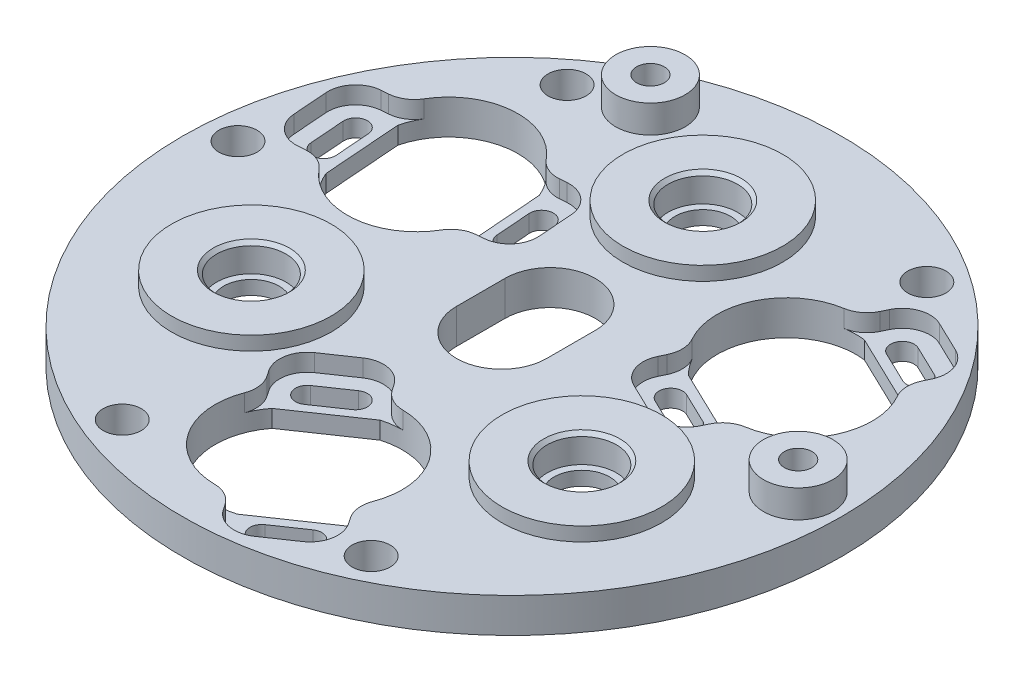
SolidWorks part; units mm, degrees
note: The reader was unsure of these and kept them because the rebuilt part matched: shared geometry of "Esquisse8<2>".
ref_plane "Plan de face" through (0, 0, 0) normal (0, 0, 1) x (1, 0, 0)
ref_plane "Plan de dessus" through (0, 0, 0) normal (0, 1, 0) x (1, 0, 0)
ref_plane "Plan de droite" through (0, 0, 0) normal (1, 0, 0) x (0, 0, -1)
sketch "Sketch2" plane through (0, 0, 0) normal (1, 0, 0) x (0, 0, -1)
  line L0 (27.5, 24.4363) -> (27.5, -19.6412) construction
  line L1 (0, -21.9713) -> (0, 23.6588) construction
  line L2 (-10.4637, 0) -> (17.1572, 0) construction
  line L3 (21, 0) -> (21, -3)
  line L5 (22.5, -1) -> (22.5, 3)
  line L7 (22.5, -1) -> (23.5, -1)
  line L8 (23.5, -1) -> (23.5, -3)
  line L9 (23.5, -3) -> (21, -3)
  line L11 (16, 3) -> (16, -4)
  line L12 (16, -4) -> (17.5, -4)
  line L13 (17.5, -4) -> (17.5, 0)
  line L14 (17.5, 0) -> (21, 0)
  line L20 (22.5, 3) -> (16, 3)
  dimension "D1" = 27.5
  dimension "D2" = 4
  dimension "D3" = 2
  dimension "D4" = 3
  dimension "D5" = 5
  dimension "D6" = 4
  dimension "D7" = 1.5
  dimension "D8" = 10
  dimension "D9" = 1.5
  dimension "D10" = 4
revolve "Revolve1" add sketch "Sketch2" angle 360 about L0
pattern_circular "CirPattern1" count 3 over 360 about axis through (0, 0, 0) along (0, 1, 0) of bodies 104
sketch "Sketch3" plane through (0, 0, 0) normal (0, 1, 0) x (1, 0, 0)
  line L0 (0, 0) -> (41.25, 0) construction
  line L1 (0, 0) -> (0, 47.5) construction
  line L2 (0, 0) -> (-17.433, 37.3852) construction
  line L3 (0, 0) -> (0, -30) construction
  line L4 (0, 0) -> (-25.9808, 15) construction
  line L5 (0, 0) -> (25.9808, 15) construction
  line L6 (0, -1.5) -> (0, 5.5) construction
  line L7 (-6.5, -1.5) -> (-6.5, 5.5)
  line L8 (6.5, -1.5) -> (6.5, 5.5)
  circle A0 centre (0, 0) radius 47.5
  circle A1 centre (0, 27.5) radius 6.5
  circle A2 centre (23.8157, -13.75) radius 6.5
  circle A3 centre (-23.8157, -13.75) radius 6.5
  circle A4 centre (0, 0) radius 27.5 construction
  arc A5 (-6.5, -1.5) -> (6.5, -1.5) centre (0, -1.5) ccw
  arc A6 (6.5, 5.5) -> (-6.5, 5.5) centre (0, 5.5) ccw
  circle A12 centre (0, 0) radius 7.5 construction
  circle A13 centre (-23.8157, -13.75) radius 11.5
  circle A14 centre (23.8157, -13.75) radius 11.5
  circle A15 centre (0, 27.5) radius 11.5
  circle A26 centre (0, 0) radius 30 construction
  circle A27 centre (0, 0) radius 41.25 construction
  circle A28 centre (0, -30) radius 1.7 construction
  circle A29 centre (-25.9808, 15) radius 1.7 construction
  circle A30 centre (25.9808, 15) radius 1.7 construction
  circle A31 centre (-17.433, 37.3852) radius 1.2 construction
  circle A32 centre (41.25, 0) radius 1.2 construction
  circle A33 centre (0, -30) radius 6 construction
  circle A34 centre (0, -30) radius 10
  circle A35 centre (25.9808, 15) radius 6 construction
  circle A36 centre (25.9808, 15) radius 10
  circle A37 centre (-25.9808, 15) radius 6 construction
  circle A38 centre (-25.9808, 15) radius 10
  circle A39 centre (-17.433, 37.3852) radius 2 construction
  circle A40 centre (-17.433, 37.3852) radius 4 construction
  circle A41 centre (41.25, 0) radius 2 construction
  circle A42 centre (41.25, 0) radius 4 construction
  circle A43 centre (-23.8157, -13.75) radius 6.5 construction
  point P17 (0, 2)
  point P35 (0, 0)
  dimension "D1" = 95
  dimension "D7" = 25
  dimension "D10" = 15
  dimension "D2" = 23
  dimension "D5" = 3.4
  dimension "D6" = 3
  dimension "D11" = 2
  dimension "D12" = 12
  dimension "D3" = 82.5
  dimension "D4" = 60
  dimension "D8" = 2.4
  dimension "D9" = 4
  dimension "D13" = 20
  dimension "D16" = 6.5
  dimension "D14" = 1.5
  dimension "D15" = 5.5
extrude "Boss-Extrude3" add sketch "Sketch3" along normal blind 5 from surface at -4
sketch "Esquisse4" plane through (0, 0, 0) normal (1, 0, 0) x (0, 0, -1)
  line L0 (-30, 11.1476) -> (-30, -4.6583) construction
  line L1 (0, 0) -> (0, 30.7253) construction
  line L2 (-38, -4.6) -> (-38, -0.6)
  line L3 (-38, -0.6) -> (-38.4, -0.6)
  line L4 (-38.4, -0.6) -> (-38.4, 0.5)
  line L5 (-38.4, 0.5) -> (-38, 0.5)
  line L6 (-38, 0.5) -> (-38, 1.5)
  line L8 (-40, 1.5) -> (-40, -6.1)
  line L10 (-40, 1.5) -> (-38, 1.5)
  line L11 (-40, -6.1) -> (-36.5, -6.1)
  line L14 (-36.5, -6.1) -> (-36.5, -4.6)
  line L15 (-36.5, -4.6) -> (-38, -4.6)
  line L16 (47.5, 1) -> (-47.5, 1) construction
  dimension "D1" = 4
  dimension "D2" = 8.4
  dimension "D3" = 8
  dimension "D4" = 2
  dimension "D5" = 0.5
  dimension "D6" = 1
  dimension "D7" = 1.1
  dimension "D8" = 1.5
  dimension "D9" = 1.5
revolve "Révolution1" add sketch "Esquisse4" angle 360 about L0
pattern_circular "Répétition circulaire1" count 3 over 360 about axis through (0, 0, 0) along (0, 1, 0) of "Révolution1"
sketch "Esquisse6" plane through (0, 1, 0) normal (0, 1, 0) x (1, 0, 0)
  line L0 (0, 27.5) -> (25.9808, 15) construction
  line L3 (23.2774, 16.3007) -> (27.783, 14.1329) construction
  line L4 (27.6129, 25.3119) -> (32.1186, 23.1442)
  line L5 (18.9418, 7.2894) -> (23.4475, 5.1216)
  line L6 (2.4781, -28.3091) -> (-1.6521, -31.1272) construction
  line L7 (8.1143, -36.5695) -> (3.9841, -39.3876)
  line L8 (-3.1581, -20.0488) -> (-7.2883, -22.8669)
  line L9 (-25.7555, 12.0085) -> (-26.1309, 16.9944) construction
  line L10 (-35.7272, 11.2575) -> (-36.1027, 16.2434)
  line L11 (-15.7837, 12.7594) -> (-16.1592, 17.7453)
  arc A3 (27.6129, 25.3119) -> (18.9418, 7.2894) centre (23.2774, 16.3007) ccw
  arc A4 (23.4475, 5.1216) -> (32.1186, 23.1442) centre (27.783, 14.1329) ccw
  arc A5 (8.1143, -36.5695) -> (-3.1581, -20.0488) centre (2.4781, -28.3091) ccw
  arc A6 (-7.2883, -22.8669) -> (3.9841, -39.3876) centre (-1.6521, -31.1272) ccw
  arc A7 (-35.7272, 11.2575) -> (-15.7837, 12.7594) centre (-25.7555, 12.0085) ccw
  arc A8 (-16.1592, 17.7453) -> (-36.1027, 16.2434) centre (-26.1309, 16.9944) ccw
  point P4 (25.5302, 15.2168)
  point P15 (0.413, -29.7182)
  point P22 (-25.9432, 14.5014)
  point P27 (0, 0)
  dimension "D3" = 10
  dimension "D1" = 3
  dimension "D2" = 2
  dimension "D4" = 3
extrude "Enlèv. mat.-Extru.2" cut sketch "Esquisse6" against normal through all both and the other way through all
chamfer "Chanfrein1" distance 0.5 angle 45 3 edges at (19.4856, 3, 11.25) (0, 3, -22.5) (-19.4856, 3, 11.25)
fillet "Congé1" radius 1 6 edges at (18.1865, 0, 10.5) (15.1554, 0, 8.75) (0, 0, -21) (0, 0, -17.5) (-18.1865, 0, 10.5) (-15.1554, 0, 8.75)
chamfer "Chanfrein3" distance 1.5 angle 45 3 edges at (0, -4, -17.5) (15.1554, -4, 8.75) (-15.1554, -4, 8.75)
sketch "Esquisse7" plane through (0, 1, 0) normal (0, 1, 0) x (1, 0, 0)
  line L0 (5.3932, -41.4527) -> (9.5234, -38.6346) construction
  line L1 (3.1387, -38.1485) -> (7.2689, -35.3304)
  line L2 (7.6477, -44.7568) -> (11.7779, -41.9387)
  line L3 (-8.6973, -20.8018) -> (-4.5672, -17.9837) construction
  line L4 (-10.9518, -17.4977) -> (-6.8217, -14.6796)
  line L5 (-6.4428, -24.106) -> (-2.3127, -21.2879)
  line L6 (-38.896, 20.0444) -> (-35.5706, 20.2948)
  line L7 (-7.2883, -22.8669) -> (-3.1581, -20.0488) construction
  line L8 (8.1143, -36.5695) -> (3.9841, -39.3876) construction
  line L9 (7.4583, -40.0436) -> (-6.6323, -19.3928) construction
  line L10 (-9.9124, -36.7635) -> (10.7384, -22.6729) construction
  line L11 (2.0891, -43.7071) -> (0.2095, -40.9524)
  line L12 (12.8275, -36.3801) -> (10.9479, -33.6254)
  line L13 (-12.0015, -23.0563) -> (-10.1219, -25.811)
  line L14 (-1.263, -15.7292) -> (0.6166, -18.4839)
  line L15 (8.1143, -36.5695) -> (3.9841, -39.3876)
  line L16 (-7.2883, -22.8669) -> (-3.1581, -20.0488)
  line L17 (-37.9198, 7.0811) -> (-34.5944, 7.3315)
  line L18 (-35.7272, 11.2575) -> (-36.1027, 16.2434)
  line L19 (-16.1592, 17.7453) -> (-15.7837, 12.7594)
  line L20 (-12.9904, 8.9584) -> (-16.3158, 8.708)
  line L21 (-13.9666, 21.9217) -> (-17.2921, 21.6713)
  line L22 (-26.8819, 26.9661) -> (-25.0045, 2.0367) construction
  line L23 (-38.4079, 13.5627) -> (-13.4785, 15.4401) construction
  line L24 (-38.5957, 16.0557) -> (-38.2202, 11.0698) construction
  line L25 (-34.6069, 16.3561) -> (-34.2315, 11.3702)
  line L26 (-42.5844, 15.7553) -> (-42.2089, 10.7694)
  line L27 (-13.6662, 17.933) -> (-13.2908, 12.9471) construction
  line L28 (-9.6775, 18.2334) -> (-9.3021, 13.2475)
  line L29 (-17.655, 17.6327) -> (-17.2795, 12.6468)
  line L30 (36.807, 23.6628) -> (35.3611, 20.6576)
  line L31 (25.0923, 29.299) -> (23.6465, 26.2939)
  line L32 (27.6129, 25.3119) -> (32.1186, 23.1442)
  line L33 (23.4475, 5.1216) -> (18.9418, 7.2894)
  line L34 (14.2534, 6.7708) -> (15.6993, 9.7759)
  line L35 (25.9681, 1.1346) -> (27.4139, 4.1397)
  line L36 (36.7943, 9.7973) -> (14.2661, 20.6362) construction
  line L37 (30.9496, 26.4809) -> (20.1108, 3.9527) construction
  line L38 (33.2025, 25.397) -> (28.6968, 27.5648) construction
  line L39 (31.4682, 21.7925) -> (26.9626, 23.9602)
  line L40 (34.9367, 29.0015) -> (30.431, 31.1693)
  line L41 (22.3636, 2.8688) -> (17.8579, 5.0366) construction
  line L42 (20.6294, -0.7357) -> (16.1237, 1.4321)
  line L43 (24.0978, 6.4733) -> (19.5922, 8.6411)
  arc A0 (3.1387, -38.1485) -> (7.6477, -44.7568) centre (5.3932, -41.4527) ccw
  arc A1 (11.7779, -41.9387) -> (7.2689, -35.3304) centre (9.5234, -38.6346) ccw
  arc A2 (-10.9518, -17.4977) -> (-6.4428, -24.106) centre (-8.6973, -20.8018) ccw
  arc A3 (-2.3127, -21.2879) -> (-6.8217, -14.6796) centre (-4.5672, -17.9837) ccw
  arc A4 (-7.2883, -22.8669) -> (3.9841, -39.3876) centre (-1.6521, -31.1272) ccw construction
  arc A5 (8.1143, -36.5695) -> (-3.1581, -20.0488) centre (2.4781, -28.3091) ccw construction
  arc A6 (8.1143, -36.5695) -> (10.9479, -33.6254) centre (2.4781, -28.3091) ccw
  arc A7 (-7.2883, -22.8669) -> (-10.1219, -25.811) centre (-1.6521, -31.1272) ccw
  arc A8 (0.2095, -40.9524) -> (3.9841, -39.3876) centre (-1.6521, -31.1272) ccw
  arc A9 (0.6166, -18.4839) -> (-3.1581, -20.0488) centre (2.4781, -28.3091) ccw
  arc A10 (-35.7272, 11.2575) -> (-34.5944, 7.3315) centre (-25.7555, 12.0085) ccw
  arc A11 (-35.5706, 20.2948) -> (-36.1027, 16.2434) centre (-26.1309, 16.9944) ccw
  arc A12 (-16.1592, 17.7453) -> (-17.2921, 21.6713) centre (-26.1309, 16.9944) ccw
  arc A13 (-16.3158, 8.708) -> (-15.7837, 12.7594) centre (-25.7555, 12.0085) ccw
  arc A14 (-34.6069, 16.3561) -> (-42.5844, 15.7553) centre (-38.5957, 16.0557) ccw
  arc A15 (-42.2089, 10.7694) -> (-34.2315, 11.3702) centre (-38.2202, 11.0698) ccw
  arc A16 (-9.6775, 18.2334) -> (-17.655, 17.6327) centre (-13.6662, 17.933) ccw
  arc A17 (-17.2795, 12.6468) -> (-9.3021, 13.2475) centre (-13.2908, 12.9471) ccw
  arc A18 (27.6129, 25.3119) -> (23.6465, 26.2939) centre (23.2774, 16.3007) ccw
  arc A19 (35.3611, 20.6576) -> (32.1186, 23.1442) centre (27.783, 14.1329) ccw
  arc A20 (23.4475, 5.1216) -> (27.4139, 4.1397) centre (27.783, 14.1329) ccw
  arc A21 (15.6993, 9.7759) -> (18.9418, 7.2894) centre (23.2774, 16.3007) ccw
  arc A22 (31.4682, 21.7925) -> (34.9367, 29.0015) centre (33.2025, 25.397) ccw
  arc A23 (30.431, 31.1693) -> (26.9626, 23.9602) centre (28.6968, 27.5648) ccw
  arc A24 (20.6294, -0.7357) -> (24.0978, 6.4733) centre (22.3636, 2.8688) ccw
  arc A25 (19.5922, 8.6411) -> (16.1237, 1.4321) centre (17.8579, 5.0366) ccw
  point P2 (7.4583, -40.0436)
  point P7 (-6.6323, -19.3928)
  point P20 (6.0492, -37.9785)
  point P21 (-5.2232, -21.4579)
  point P30 (0.413, -29.7182)
  point P40 (-38.4079, 13.5627)
  point P45 (-13.4785, 15.4401)
  point P72 (30.9496, 26.4809)
  point P77 (20.1108, 3.9527)
  point P102 (0, 0)
  circle M14 centre (-23.8157, -13.75) radius 11.5
  circle M15 centre (23.8157, -13.75) radius 11.5
  circle M16 centre (0, 27.5) radius 11.5
  line M17 (-7.2883, -22.8669) -> (-3.1581, -20.0488)
  arc M18 (-3.1581, -20.0488) -> (8.1143, -36.5695) centre (2.4781, -28.3091) cw
  line M19 (8.1143, -36.5695) -> (3.9841, -39.3876)
  arc M20 (3.9841, -39.3876) -> (-7.2883, -22.8669) centre (-1.6521, -31.1272) cw
  line M21 (23.4475, 5.1216) -> (18.9418, 7.2894)
  arc M22 (18.9418, 7.2894) -> (27.6129, 25.3119) centre (23.2774, 16.3007) cw
  line M23 (27.6129, 25.3119) -> (32.1186, 23.1442)
  arc M24 (32.1186, 23.1442) -> (23.4475, 5.1216) centre (27.783, 14.1329) cw
  line M25 (-16.1592, 17.7453) -> (-15.7837, 12.7594)
  arc M26 (-15.7837, 12.7594) -> (-35.7272, 11.2575) centre (-25.7555, 12.0085) cw
  line M27 (-35.7272, 11.2575) -> (-36.1027, 16.2434)
  arc M28 (-36.1027, 16.2434) -> (-16.1592, 17.7453) centre (-26.1309, 16.9944) cw
  line M29 (-6.5, -1.5) -> (-6.5, 5.5)
  arc M30 (-6.5, 5.5) -> (6.5, 5.5) centre (0, 5.5) cw
  line M31 (6.5, 5.5) -> (6.5, -1.5)
  arc M32 (6.5, -1.5) -> (-6.5, -1.5) centre (0, -1.5) cw
  dimension "D2" = 4
  dimension "D1" = 12.5
  dimension "D3" = 3
extrude "Enlèv. mat.-Extru.3" cut sketch "Esquisse7" against normal blind 2.5 contours A3 L4 A2 M18 M32 M14 M20 M17 | A3 L14 M18 | A2 L13 M20 | L2 A1 A0 M18 M19 M20 | A0 L11 M20 | A1 L12 M18 | A25 L42 A24 A20 M31 M15 M21 M22 | A25 A21 L34 | A24 L35 M24 | L40 A23 A18 A22 M23 M24 | A22 A19 L30 | A23 L31 M22 | A17 L28 A16 A12 M26 M29 M30 M16 M25 | A16 L21 M28 | A17 A13 L20 | A15 A10 A14 L26 M27 M28 | A15 L17 M26 | A14 A11 L6
sketch "Esquisse8" plane through (0, 1, 0) normal (0, 1, 0) x (1, 0, 0)
  line L0 (-8.6973, -20.8018) -> (-4.5672, -17.9837) construction
  line L1 (-9.6555, -19.3976) -> (-5.5253, -16.5795)
  line L2 (-7.7392, -22.2061) -> (-3.609, -19.388)
  line L3 (5.3932, -41.4527) -> (9.5234, -38.6346) construction
  line L4 (4.435, -40.0484) -> (8.5652, -37.2303)
  line L5 (6.3514, -42.8569) -> (10.4815, -40.0388)
  line L6 (22.3636, 2.8688) -> (17.8579, 5.0366) construction
  line L7 (21.6265, 1.3369) -> (17.1209, 3.5047)
  line L8 (23.1006, 4.4007) -> (18.595, 6.5685)
  line L9 (33.2025, 25.397) -> (28.6968, 27.5648) construction
  line L10 (32.4654, 23.8651) -> (27.9598, 26.0328)
  line L11 (33.9395, 26.9289) -> (29.4339, 29.0967)
  line L12 (-13.2908, 12.9471) -> (-13.6662, 17.933) construction
  line L13 (-14.986, 12.8195) -> (-15.3614, 17.8054)
  line L14 (-11.5956, 13.0748) -> (-11.971, 18.0607)
  line L15 (-38.2202, 11.0698) -> (-38.5957, 16.0557) construction
  line L16 (-39.9154, 10.9421) -> (-40.2909, 15.928)
  line L17 (-36.525, 11.1975) -> (-36.9005, 16.1833)
  line L18 (-9.5858, -25.0398) -> (-0.297, -18.7019)
  line L19 (1.123, -40.7345) -> (10.4118, -34.3965)
  line L20 (8.1143, -36.5695) -> (3.9841, -39.3876) construction
  line L21 (-7.2883, -22.8669) -> (-3.1581, -20.0488) construction
  line L22 (-7.2883, -22.8669) -> (-3.1581, -20.0488)
  line L23 (8.1143, -36.5695) -> (3.9841, -39.3876)
  line L24 (-16.8923, 20.8214) -> (-16.0478, 9.6082)
  line L25 (-16.1592, 17.7453) -> (-15.7837, 12.7594)
  line L26 (-35.7272, 11.2575) -> (-36.1027, 16.2434)
  line L27 (-35.8386, 19.3946) -> (-34.9942, 8.1814)
  line L28 (26.478, 4.2184) -> (16.3448, 9.0937)
  line L29 (23.4475, 5.1216) -> (18.9418, 7.2894)
  line L30 (27.6129, 25.3119) -> (32.1186, 23.1442)
  line L31 (34.7156, 21.3398) -> (24.5824, 26.2151)
  arc A0 (-9.6555, -19.3976) -> (-7.7392, -22.2061) centre (-8.6973, -20.8018) ccw
  arc A1 (-3.609, -19.388) -> (-5.5253, -16.5795) centre (-4.5672, -17.9837) ccw
  arc A2 (4.435, -40.0484) -> (6.3514, -42.8569) centre (5.3932, -41.4527) ccw
  arc A3 (10.4815, -40.0388) -> (8.5652, -37.2303) centre (9.5234, -38.6346) ccw
  arc A4 (21.6265, 1.3369) -> (23.1006, 4.4007) centre (22.3636, 2.8688) ccw
  arc A5 (18.595, 6.5685) -> (17.1209, 3.5047) centre (17.8579, 5.0366) ccw
  arc A6 (32.4654, 23.8651) -> (33.9395, 26.9289) centre (33.2025, 25.397) ccw
  arc A7 (29.4339, 29.0967) -> (27.9598, 26.0328) centre (28.6968, 27.5648) ccw
  arc A8 (-14.986, 12.8195) -> (-11.5956, 13.0748) centre (-13.2908, 12.9471) ccw
  arc A9 (-11.971, 18.0607) -> (-15.3614, 17.8054) centre (-13.6662, 17.933) ccw
  arc A10 (-39.9154, 10.9421) -> (-36.525, 11.1975) centre (-38.2202, 11.0698) ccw
  arc A11 (-36.9005, 16.1833) -> (-40.2909, 15.928) centre (-38.5957, 16.0557) ccw
  arc A12 (-7.2883, -22.8669) -> (-10.1219, -25.811) centre (-1.6521, -31.1272) ccw construction
  arc A13 (10.9479, -33.6254) -> (0.6166, -18.4839) centre (2.4781, -28.3091) ccw construction
  arc A14 (-10.1219, -25.811) -> (0.2095, -40.9524) centre (-1.6521, -31.1272) ccw construction
  arc A15 (0.6166, -18.4839) -> (-3.1581, -20.0488) centre (2.4781, -28.3091) ccw construction
  arc A16 (0.2095, -40.9524) -> (3.9841, -39.3876) centre (-1.6521, -31.1272) ccw construction
  arc A17 (8.1143, -36.5695) -> (10.9479, -33.6254) centre (2.4781, -28.3091) ccw construction
  arc A18 (-0.297, -18.7019) -> (-3.1581, -20.0488) centre (2.4781, -28.3091) ccw
  arc A19 (-7.2883, -22.8669) -> (-9.5858, -25.0398) centre (-1.6521, -31.1272) ccw
  arc A20 (1.123, -40.7345) -> (3.9841, -39.3876) centre (-1.6521, -31.1272) ccw
  arc A21 (8.1143, -36.5695) -> (10.4118, -34.3965) centre (2.4781, -28.3091) ccw
  arc A22 (-16.1592, 17.7453) -> (-16.8923, 20.8214) centre (-26.1309, 16.9944) ccw
  arc A23 (-16.0478, 9.6082) -> (-15.7837, 12.7594) centre (-25.7555, 12.0085) ccw
  arc A24 (-35.8386, 19.3946) -> (-36.1027, 16.2434) centre (-26.1309, 16.9944) ccw
  arc A25 (-35.7272, 11.2575) -> (-34.9942, 8.1814) centre (-25.7555, 12.0085) ccw
  arc A26 (23.4475, 5.1216) -> (26.478, 4.2184) centre (27.783, 14.1329) ccw
  arc A27 (16.3448, 9.0937) -> (18.9418, 7.2894) centre (23.2774, 16.3007) ccw
  arc A28 (34.7156, 21.3398) -> (32.1186, 23.1442) centre (27.783, 14.1329) ccw
  arc A29 (27.6129, 25.3119) -> (24.5824, 26.2151) centre (23.2774, 16.3007) ccw
  point P4 (-6.6323, -19.3928)
  point P9 (7.4583, -40.0436)
  point P18 (20.1108, 3.9527)
  point P27 (30.9496, 26.4809)
  point P36 (-13.4785, 15.4401)
  point P45 (-38.4079, 13.5627)
  point P98 (0, 0)
  dimension "D1" = 1.7
  dimension "D2" = 0.5
  dimension "D3" = 0.5
  dimension "D4" = 3
extrude "Enlèv. mat.-Extru.4" cut sketch "Esquisse8" against normal up to next
extrude "Boss.-Extru.1" add sketch "Esquisse8<2>" against normal up to surface (2.5 mm away) from surface at -2.5 contours L23 A21 L19 A20 | L22 A19 L18 A18 | L26 A25 L27 A24 | L30 A29 L31 A28 | L24 A23 L25 A22 | L28 A27 L29 A26 starting at face at (30.9496, -1.5, -26.4809)
sketch "Esquisse8<2>" plane through (0, 1, 0) normal (0, 1, 0) x (1, 0, 0) same geometry as "Esquisse8"
fillet "Congé2" radius 4 12 edges at (15.6993, -0.25, -9.7759) (27.4139, -0.25, -4.1397) (35.3611, -0.25, -20.6576) (23.6465, -0.25, -26.2939) (-17.2921, -0.25, -21.6713) (-35.5706, -0.25, -20.2948) (-34.5944, -0.25, -7.3315) (-16.3158, -0.25, -8.708) (0.6166, -0.25, 18.4839) (-10.1219, -0.25, 25.811) (0.2095, -0.25, 40.9524) (10.9479, -0.25, 33.6254)
sketch "Esquisse9" plane through (0, 1, 0) normal (0, 1, 0) x (1, 0, 0)
  circle A0 centre (-17.433, 37.3852) radius 2
  circle A1 centre (-17.433, 37.3852) radius 5
  circle A2 centre (41.25, 0) radius 2
  circle A3 centre (41.25, 0) radius 5
  dimension "D1" = 4
  dimension "D2" = 10
extrude "Boss.-Extru.2" add sketch "Esquisse9" along normal blind 4
sketch "Esquisse12" plane through (0, 1, 0) normal (0, 1, 0) x (1, 0, 0)
  point P0 (-17.433, 37.3852)
  point P3 (41.25, 0)
hole_wizard "M2 Clearance Hole1" positions "Esquisse12" profile "Esquisse11" hole size "M2" standard "ANSI Metric" end condition through all
sketch "Esquisse11" plane through (-17.433, 1, -37.3852) normal (1, 0, 0) x (0, 0, 1)
  line L0 (0, 0) -> (0, 5)
  line L1 (0, 5) -> (1.2, 5)
  line L2 (1.2, 5) -> (1.2, 0)
  line L5 (1.2, 0) -> (0, 0)
  line L11 (0, -6.35) -> (0, 107.95) construction
  dimension "Thru Hole Dia." = 2.4
  dimension "Thru Hole Depth" = 5
sketch "Esquisse13" plane through (0, 1, 0) normal (0, 1, 0) x (1, 0, 0)
  line L0 (0, 0) -> (0, 47.5) construction
  line L1 (0, 0) -> (47.5, 0) construction
  line L2 (0, 0) -> (42.6321, 5.6126) construction
  line L3 (0, 0) -> (24.3555, 35.4374) construction
  line L4 (0, 0) -> (18.512, -38.8112) construction
  line L5 (0, 0) -> (-16.4554, -39.7268) construction
  line L6 (0, 0) -> (-42.8674, 3.3737) construction
  line L7 (0, 0) -> (-26.1767, 34.1142) construction
  circle A0 centre (0, 0) radius 47.5 construction
  circle A1 centre (0, 0) radius 43 construction
  circle A2 centre (24.3555, 35.4374) radius 2.75 construction
  circle A3 centre (42.6321, 5.6126) radius 2.75 construction
  circle A4 centre (18.512, -38.8112) radius 2.75 construction
  circle A5 centre (-16.4554, -39.7268) radius 2.75 construction
  circle A6 centre (-42.8674, 3.3737) radius 2.75 construction
  circle A7 centre (-26.1767, 34.1142) radius 2.75 construction
  point P22 (0, 0)
  dimension "D1" = 4.5
  dimension "D2" = 7.5
  dimension "D4" = 5.5
  dimension "D3" = 34.5
  dimension "D5" = 3
sketch "Esquisse16" plane through (0, 1, 0) normal (0, 1, 0) x (1, 0, 0)
  point P0 (-26.1767, 34.1142)
  point P3 (24.3555, 35.4374)
  point P6 (18.512, -38.8112)
  point P9 (-16.4554, -39.7268)
  point P12 (-42.8674, 3.3737)
hole_wizard "M5 Clearance Hole1" positions "Esquisse16" profile "Esquisse15" hole size "M5" standard "ANSI Metric" end condition up to next
sketch "Esquisse15" plane through (-26.1767, 1, -34.1142) normal (1, 0, 0) x (0, 0, 1)
  line L0 (0, 0) -> (0, 5)
  line L1 (0, 5) -> (2.75, 5)
  line L2 (2.75, 5) -> (2.75, 0)
  line L5 (2.75, 0) -> (0, 0)
  line L11 (0, -6.35) -> (0, 107.95) construction
  dimension "Thru Hole Dia." = 5.5
  dimension "Thru Hole Depth" = 5
